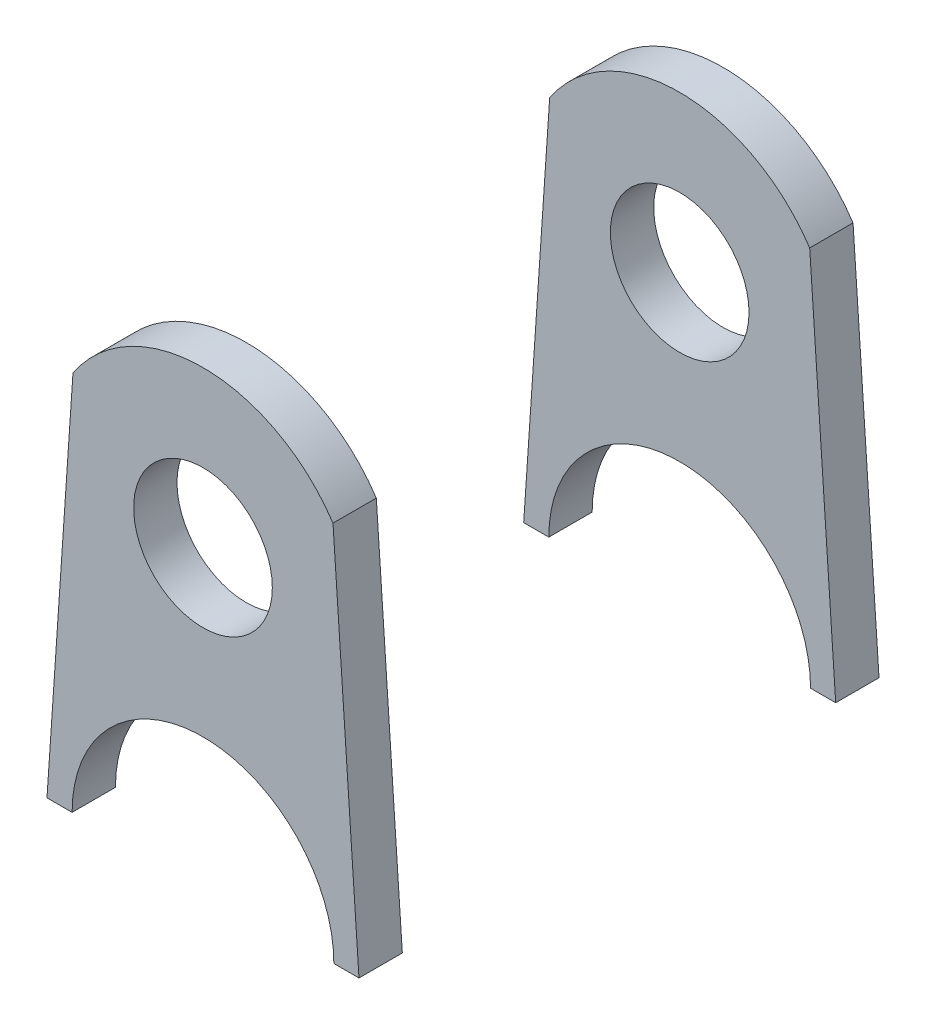
SolidWorks part; units mm, degrees
ref_plane "Front Plane" through (0, 0, 0) normal (0, 0, 1) x (1, 0, 0)
ref_plane "Top Plane" through (0, 0, 0) normal (0, 1, 0) x (1, 0, 0)
ref_plane "Right Plane" through (0, 0, 0) normal (1, 0, 0) x (0, 0, -1)
sketch "Sketch1" plane through (0, 0, 0) normal (0, 0, 1) x (1, 0, 0)
  line L16 (-1.5, 0) -> (0, 21.9749)
  line L17 (15, 21.9749) -> (16.5, 0)
  circle A0 centre (7.5, 17) radius 4
  arc A1 (15, 21.9749) -> (0, 21.9749) centre (7.5, 17) ccw
  circle A3 centre (7.5, 0) radius 7.55
  arc A4 (-1.4165, 1.223) -> (16.4165, 1.223) centre (7.5, 0) ccw
extrude "Boss-Extrude2" add sketch "Sketch1" along normal blind 15 and the other way blind 15 contours L16 A4 L17 A1 A0 A3 region at (7.5, 11.6389, 0)
sketch "Sketch5" plane through (0, 0, 0) normal (0, 1, 0) x (1, 0, 0)
  line L3 (-1.5, 15) -> (-1.5, -15) construction
  line L4 (-1.5, 12.5) -> (-1.5, -12.5)
  line L5 (-1.5, -12.5) -> (16.5, -12.5)
  line L6 (16.5, 15) -> (16.5, -15) construction
  line L7 (16.5, -12.5) -> (16.5, 12.5)
  line L8 (16.5, 12.5) -> (-1.5, 12.5)
extrude "Cut-Extrude4" cut sketch "Sketch5" along normal through all and the other way through all
sketch "Sketch6" plane through (0, 0, 15) normal (0, 0, 1) x (1, 0, 0)
  line L0 (7.5, 0) -> (-2.9473, 0)
  line L1 (-2.9473, 0) -> (-2.9473, -10.0053)
  line L2 (-2.9473, -10.0053) -> (19.3059, -10.0053)
  line L3 (19.3059, -10.0053) -> (19.3059, 0)
  line L4 (19.3059, 0) -> (7.5, 0)
extrude "Cut-Extrude5" cut sketch "Sketch6" against normal through all and the other way through all
